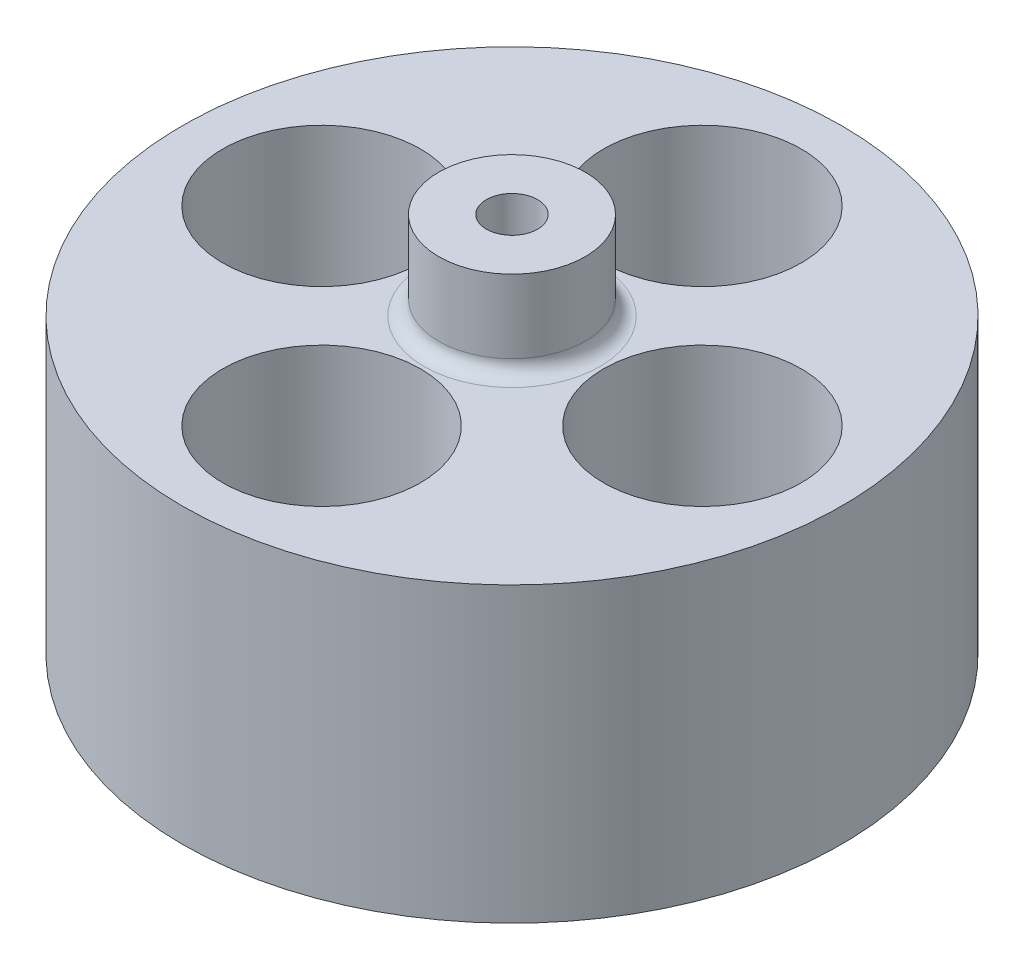
SolidWorks part; units mm, degrees
material "6061 Alloy"
ref_plane "Front Plane" through (0, 0, 0) normal (0, 0, 1) x (1, 0, 0)
ref_plane "Top Plane" through (0, 0, 0) normal (0, 1, 0) x (1, 0, 0)
ref_plane "Right Plane" through (0, 0, 0) normal (1, 0, 0) x (0, 0, -1)
sketch "Sketch1" plane through (0, 0, 0) normal (0, 1, 0) x (1, 0, 0)
  circle A0 centre (0, 0) radius 22.5
  dimension "D1" = 45
extrude "Boss-Extrude1" add sketch "Sketch1" along normal blind 20
sketch "Sketch2" plane through (0, 20, 0) normal (0, 1, 0) x (1, 0, 0)
  line L0 (0, -11) -> (0, 11) construction
  line L1 (-11, 0) -> (11, 0) construction
  line L2 (0, 19.75) -> (16.0728, 19.75) construction
  line L3 (0, 22.5) -> (15.4299, 22.5) construction
  circle A0 centre (0, 13) radius 6.75
  circle A1 centre (0, 0) radius 22.5 construction
  dimension "D1" = 13.5
  dimension "D2" = 13
  dimension "D3" = 2.75
extrude "Cut-Extrude1" cut sketch "Sketch2" against normal blind 10
sketch "Sketch3" plane through (0, 10, 0) normal (0, 1, 0) x (1, 0, 0)
  circle A0 centre (0, 13) radius 2
  dimension "D1" = 4
extrude "Cut-Extrude2" cut sketch "Sketch3" against normal blind 35
pattern_circular "CirPattern1" count 4 over 360 about axis through (0, 20, 0) along (0, 1, 0) of "Cut-Extrude1", "Cut-Extrude2"
sketch "Sketch6" plane through (0, 20, 0) normal (0, 1, 0) x (1, 0, 0)
  circle A0 centre (0, 0) radius 1.75
  dimension "D2" = 3.5
extrude "Cut-Extrude4" cut sketch "Sketch6" against normal blind 45
sketch "Sketch7" plane through (0, 20, 0) normal (0, 1, 0) x (1, 0, 0)
  circle A0 centre (0, 0) radius 5
  circle A1 centre (0, 0) radius 1.75
  dimension "D1" = 10
extrude "Boss-Extrude2" add sketch "Sketch7" along normal blind 6
fillet "Fillet1" radius 1 1 edges at (0, 20, 5)
